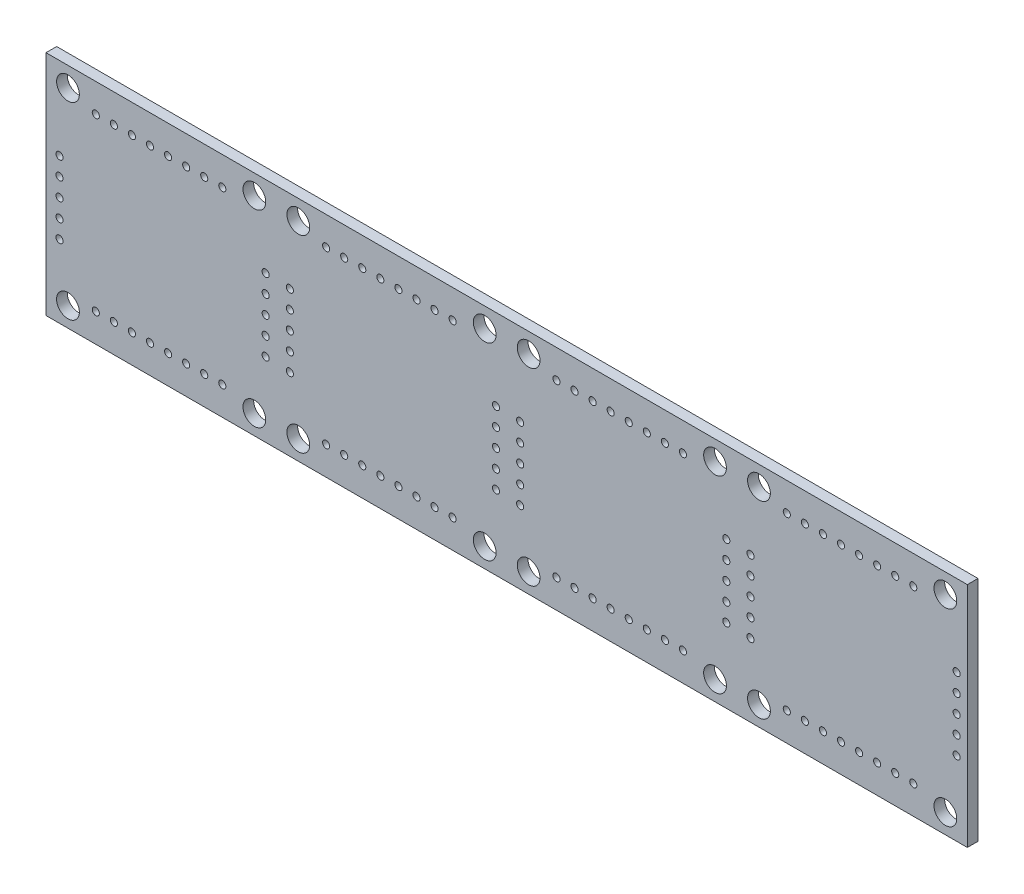
SolidWorks part; units mm, degrees
ref_plane "Front Plane" through (0, 0, 0) normal (0, 0, 1) x (1, 0, 0)
ref_plane "Top Plane" through (0, 0, 0) normal (0, 1, 0) x (1, 0, 0)
ref_plane "Right Plane" through (0, 0, 0) normal (1, 0, 0) x (0, 0, -1)
sketch "Sketch1" plane through (0, 0, 0) normal (0, 0, 1) x (1, 0, 0)
  line L0 (-28.3747, 11.4715) -> (31.6253, 11.4715) construction
  line L1 (-13.1, 13.25) -> (-13.1, -13.25) construction
  line L2 (16.1875, -16) -> (-16.1875, -16)
  line L3 (16.1875, -16) -> (16.1875, 16)
  line L4 (16.1875, 16) -> (-16.1875, 16)
  line L5 (-16.1875, -16) -> (-16.1875, 16)
  line L6 (16.1875, -16) -> (-16.1875, 16) construction
  line L7 (16.1875, 16) -> (-16.1875, -16) construction
  line L8 (-13.1, -13.25) -> (13.1, -13.25) construction
  line L9 (13.1, -13.25) -> (13.1, 13.25) construction
  line L10 (13.1, 13.25) -> (-13.1, 13.25) construction
  line L11 (-13.1, 0) -> (0, 0) construction
  line L12 (0, 0) -> (13.1, 0) construction
  circle A0 centre (-13.1, -13.25) radius 1.6
  circle A1 centre (13.1, -13.25) radius 1.6
  circle A2 centre (13.1, 13.25) radius 1.6
  circle A3 centre (-13.1, 13.25) radius 1.6
  point P2 (0, 0)
  dimension "D5" = 3.2
  dimension "D1" = 60
  dimension "D2" = 32.375
  dimension "D3" = 32
  dimension "D4" = 26.2
  dimension "D6" = 26.5
extrude "Boss-Extrude1" add sketch "Sketch1" along normal blind 1.5
sketch "Sketch3" plane through (0, 0, 0) normal (0, 0, -1) x (-1, 0, 0)
  line L0 (-24.8567, 0.1327) -> (25.1427, 0.3778) construction
  line L1 (16.1875, 16) -> (16.1875, -16) construction
  line L2 (-16.1875, -16) -> (-16.1875, 16) construction
  line L3 (-16.1875, 16) -> (16.1875, 16) construction
  circle A11 centre (-14.6875, 4.6) radius 0.5
  circle A12 centre (-14.6875, 2.06) radius 0.5
  circle A13 centre (-14.6875, -0.48) radius 0.5
  circle A14 centre (-14.6875, -3.02) radius 0.5
  circle A15 centre (-14.6875, -5.56) radius 0.5
  circle A40 centre (9.1875, 12) radius 0.5
  circle A41 centre (6.6475, 12) radius 0.5
  circle A42 centre (4.1075, 12) radius 0.5
  circle A43 centre (1.5675, 12) radius 0.5
  circle A44 centre (-0.9725, 12) radius 0.5
  circle A45 centre (-3.5125, 12) radius 0.5
  circle A46 centre (-6.0525, 12) radius 0.5
  circle A47 centre (-8.5925, 12) radius 0.5
  circle A48 centre (9.1875, -12) radius 0.5
  circle A49 centre (6.6475, -12) radius 0.5
  circle A50 centre (4.1075, -12) radius 0.5
  circle A51 centre (1.5675, -12) radius 0.5
  circle A52 centre (-0.9725, -12) radius 0.5
  circle A53 centre (-3.5125, -12) radius 0.5
  circle A54 centre (-6.0525, -12) radius 0.5
  circle A55 centre (-8.5925, -12) radius 0.5
  circle A56 centre (14.2875, 4.4) radius 0.5
  circle A57 centre (14.2875, 1.86) radius 0.5
  circle A58 centre (14.2875, -0.68) radius 0.5
  circle A59 centre (14.2875, -3.22) radius 0.5
  circle A60 centre (14.2875, -5.76) radius 0.5
  dimension "D1" = 1
  dimension "D11" = 1
  dimension "D3" = 1.5
  dimension "D4" = 11.4
  dimension "D13" = 7
  dimension "D14" = 4
  dimension "D16" = 24
  dimension "D17" = 11.6
  dimension "D18" = 1.9
  dimension "D2" = 5
  dimension "D12" = 8
  dimension "D15" = 8
  dimension "D19" = 5
extrude "Cut-Extrude1" cut sketch "Sketch3" against normal up to surface (1.5 mm away) up to face at (14.7, 13.25, 1.5)
chamfer "Chamfer1" [suppressed] distance 1 angle 45
pattern_linear "Répétition linéaire1" count 4 spacing 32.375 along (1, 0, 0) of "Boss-Extrude1", "Cut-Extrude1"
sketch "Esquisse1" plane through (0, 0, 1.5) normal (0, 0, 1) x (1, 0, 0)
  line L8 (-17.1875, 17) -> (-17.1875, -17)
  line L9 (-17.1875, -17) -> (114.3125, -17)
  line L10 (114.3125, -17) -> (114.3125, 17)
  line L11 (114.3125, 17) -> (-17.1875, 17)
  line L12 (-17.1875, 17) -> (-17.1875, -17)
  line L13 (-17.1875, -17) -> (114.3125, -17)
  line L14 (114.3125, -17) -> (114.3125, 17)
  line L15 (114.3125, 17) -> (-17.1875, 17)
  circle A1 centre (110.225, 13.25) radius 1.6 construction
  circle A2 centre (110.225, -13.25) radius 1.6 construction
  circle A3 centre (77.85, -13.25) radius 1.6 construction
  circle A4 centre (84.025, -13.25) radius 1.6 construction
  circle A5 centre (84.025, 13.25) radius 1.6 construction
  circle A6 centre (77.85, 13.25) radius 1.6 construction
  circle A7 centre (45.475, 13.25) radius 1.6 construction
  circle A8 centre (51.65, 13.25) radius 1.6 construction
  circle A9 centre (51.65, -13.25) radius 1.6 construction
  circle A10 centre (45.475, -13.25) radius 1.6 construction
  circle A11 centre (13.1, -13.25) radius 1.6 construction
  circle A12 centre (19.275, -13.25) radius 1.6 construction
  circle A13 centre (19.275, 13.25) radius 1.6 construction
  circle A14 centre (13.1, 13.25) radius 1.6 construction
  circle A15 centre (-13.1, -13.25) radius 1.6 construction
  circle A16 centre (-13.1, 13.25) radius 1.6 construction
  circle A17 centre (110.225, 13.25) radius 1.6
  circle A18 centre (110.225, -13.25) radius 1.6
  circle A19 centre (77.85, -13.25) radius 1.6
  circle A20 centre (84.025, -13.25) radius 1.6
  circle A21 centre (84.025, 13.25) radius 1.6
  circle A22 centre (77.85, 13.25) radius 1.6
  circle A23 centre (45.475, 13.25) radius 1.6
  circle A24 centre (51.65, 13.25) radius 1.6
  circle A25 centre (51.65, -13.25) radius 1.6
  circle A26 centre (45.475, -13.25) radius 1.6
  circle A27 centre (13.1, -13.25) radius 1.6
  circle A28 centre (19.275, -13.25) radius 1.6
  circle A29 centre (19.275, 13.25) radius 1.6
  circle A30 centre (13.1, 13.25) radius 1.6
  circle A31 centre (-13.1, -13.25) radius 1.6
  circle A32 centre (-13.1, 13.25) radius 1.6
  dimension "D1" = 1
sketch "Esquisse2" plane through (113.3125, 0, 0) normal (1, 0, 0) x (0, 0, -1)
  line L8 (0.5, -16.5) -> (0.5, 16.5)
  line L9 (0.5, 16.5) -> (-2, 16.5)
  line L10 (-2, 16.5) -> (-2, -16.5)
  line L11 (-2, -16.5) -> (0.5, -16.5)
  line L12 (0.5, -16.5) -> (0.5, 16.5)
  line L13 (0.5, 16.5) -> (-2, 16.5)
  line L14 (-2, 16.5) -> (-2, -16.5)
  line L15 (-2, -16.5) -> (0.5, -16.5)
  dimension "D1" = 0.5
